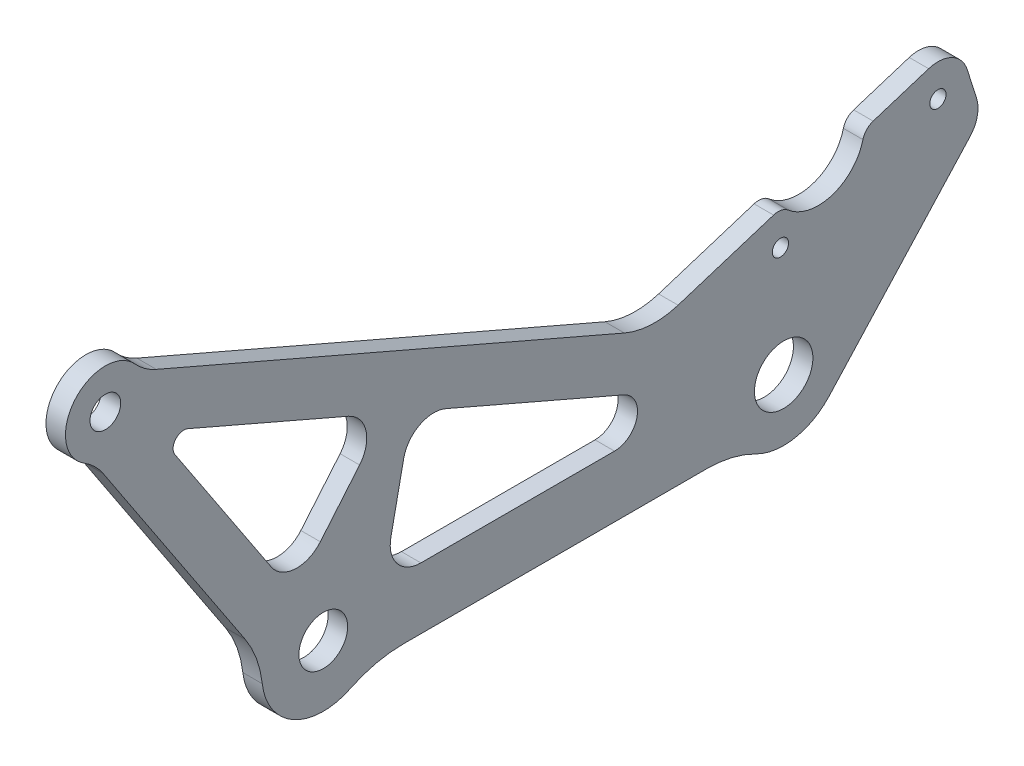
SolidWorks part; units mm, degrees
material "AISI 1020"
ref_plane "Front Plane" through (0, 0, 0) normal (0, 0, 1) x (1, 0, 0)
ref_plane "Top Plane" through (0, 0, 0) normal (0, 1, 0) x (1, 0, 0)
ref_plane "Right Plane" through (0, 0, 0) normal (1, 0, 0) x (0, 0, -1)
sketch "Sketch1" plane through (0, 0, 0) normal (1, 0, 0) x (0, 0, -1)
  line L0 (-60.7171, 0) -> (60.7171, 0)
  line L3 (0, -143.7223) -> (0, 143.7223) construction
  line L4 (-149.7529, 101.5535) -> (-94.5581, 18.1812)
  line L5 (-134.4049, 119.8783) -> (67.4524, 32.5212)
  line L6 (-75, 14) -> (75, 14) construction
  line L8 (-146, 114) -> (-75, 14) construction
  arc A20 (-134.4049, 119.8783) -> (-149.7529, 101.5535) centre (-146, 114) ccw
  arc A22 (-94.5581, 18.1812) -> (-60.7171, 0) centre (-75, 14) ccw
  arc A23 (60.7171, 0) -> (67.4524, 32.5212) centre (75, 14) ccw
  point P5 (0, 0)
  point P14 (0, 0)
  dimension "D3" = 20
  dimension "D5" = 13
  dimension "D6" = 20
  dimension "D4" = 127
  dimension "D7" = 254
  dimension "D10" = 6
  dimension "D11" = 6
  dimension "D9" = 3
  dimension "D12" = 3
  dimension "D13" = 6
  dimension "D14" = 6
  dimension "D2" = 150
  dimension "D8" = 122.6418
extrude "Boss-Extrude1" add sketch "Sketch1" along normal blind 6.35
hole_wizard "3/4 (0.75) Diameter Hole1" positions "Sketch4" profile "Sketch3" hole size "3/4" standard "ANSI Inch" end condition up to next
sketch "Sketch4" plane through (6.35, 0, 0) normal (1, 0, 0) x (0, 0, -1)
  point P5 (75, 14)
sketch "Sketch3" plane through (6.35, 14, -75) normal (0, 1, 0) x (0, 0, -1)
  line L0 (0, 0) -> (0, 6.35)
  line L1 (0, 6.35) -> (9.525, 6.35)
  line L2 (9.525, 6.35) -> (9.525, 0)
  line L5 (9.525, 0) -> (0, 0)
  line L11 (0, -6.35) -> (0, 107.95) construction
  dimension "Thru Hole Dia." = 19.05
  dimension "Thru Hole Depth" = 6.35
hole_wizard "Ø10.0 (10) Diameter Hole1" positions "Sketch9" profile "Sketch6" hole size "Ø10.0" standard "ANSI Metric" end condition up to next
sketch "Sketch9" plane through (6.35, 0, 0) normal (1, 0, 0) x (0, 0, -1)
  point P0 (-146, 114)
sketch "Sketch6" plane through (6.35, 114, 146) normal (0, 1, 0) x (0, 0, -1)
  line L0 (0, 0) -> (0, 6.35)
  line L1 (0, 6.35) -> (5, 6.35)
  line L2 (5, 6.35) -> (5, 0)
  line L5 (5, 0) -> (0, 0)
  line L11 (0, -6.35) -> (0, 107.95) construction
  dimension "Thru Hole Dia." = 10
  dimension "Thru Hole Depth" = 6.35
hole_wizard "Ø5/8\" Diameter Hole2" positions "Sketch16" profile "Sketch11" hole size "5/8" standard "ANSI Inch" end condition up to next
sketch "Sketch16" plane through (6.35, 0, 0) normal (1, 0, 0) x (0, 0, -1)
  line L0 (75, 14) -> (157.5513, 156.983)
  line L2 (0, 0) -> (0, 108.153) construction
  line L4 (-146, 114) -> (-119.4521, 194.8786)
  line L6 (-174.545, 70.324) -> (-178.0536, 59.6351) construction
  line L7 (-174.545, 70.324) -> (-178.0536, 59.6351) construction
  arc A0 (-94.5581, 18.1812) -> (-60.7171, 0) centre (-75, 14) ccw construction
  point P0 (-75, 14)
  dimension "D1" = 30
sketch "Sketch11" plane through (6.35, 14, 75) normal (0, 1, 0) x (0, 0, -1)
  line L0 (0, 0) -> (0, 6.35)
  line L1 (0, 6.35) -> (7.9375, 6.35)
  line L2 (7.9375, 6.35) -> (7.9375, 0)
  line L5 (7.9375, 0) -> (0, 0)
  line L11 (0, -6.35) -> (0, 107.95) construction
  dimension "Thru Hole Dia." = 15.875
  dimension "Thru Hole Depth" = 6.35
sketch "Sketch8" plane through (6.35, 0, 0) normal (1, 0, 0) x (0, 0, -1)
  line L2 (-54.5605, 67.8903) -> (-46.3008, 64.3157) construction
  line L3 (-52.9877, 32.028) -> (-48.7918, 52.2877)
  line L7 (-75.9573, 42.3434) -> (-63.1664, 57.6152)
  line L9 (-123.3455, 90.6494) -> (-91.9619, 43.2441)
  line L10 (-119.037, 95.7935) -> (-66.861, 73.2135)
  line L11 (19.8861, 20) -> (-43.1955, 20)
  line L12 (67.4524, 32.5212) -> (-134.4049, 119.8783) construction
  line L13 (-149.7529, 101.5535) -> (-94.5581, 18.1812) construction
  line L14 (-60.7171, 0) -> (60.7171, 0) construction
  line L15 (-84.5632, 32.0683) -> (-84.2827, 31.6447) construction
  line L16 (-55.4787, 20) -> (-55.9867, 20) construction
  line L17 (-54.5605, 67.8903) -> (-46.3008, 64.3157) construction
  line L18 (-35.0279, 59.4372) -> (22.8649, 34.3831)
  line L19 (-120.4271, 92.5814) -> (-104.3957, 79.1543) construction
  line L20 (19.8861, 27.5) -> (27.9693, 25.826) construction
  line L21 (-29.8567, 10) -> (10.3311, 10) construction
  arc A0 (-52.9877, 32.028) -> (-43.1955, 20) centre (-43.1955, 30) ccw
  arc A2 (-48.7918, 52.2877) -> (-35.0279, 59.4372) centre (-38.9996, 50.2597) cw
  arc A4 (-63.1664, 57.6152) -> (-66.861, 73.2135) centre (-70.8327, 64.0361) ccw
  arc A14 (-119.037, 95.7935) -> (-123.3455, 90.6494) centre (-120.4271, 92.5814) ccw
  arc A20 (-75.9573, 42.3434) -> (-91.9619, 43.2441) centre (-83.6236, 48.7643) cw
  arc A25 (-134.4049, 119.8783) -> (-149.7529, 101.5535) centre (-146, 114) ccw construction
  circle A27 centre (-146, 114) radius 5 construction
  arc A36 (-94.5581, 18.1812) -> (-60.7171, 0) centre (-75, 14) ccw construction
  circle A39 centre (-75, 14) radius 7.9375 construction
  arc A40 (19.8861, 20) -> (22.8649, 34.3831) centre (19.8861, 27.5) ccw
  circle A54 centre (-75, 14) radius 19.9375
  arc A55 (-55.9867, 20) -> (-84.2827, 31.6447) centre (-75, 14) ccw construction
  point P7 (-33.5049, 66.1162)
  point P19 (-33.4763, 76.1997)
  dimension "D8" = 8
  dimension "D9" = 12.0625
  dimension "D11" = 9
  dimension "D7" = 4
  dimension "D1" = 7
  dimension "D10" = 24.8576
  dimension "D2" = 15
  dimension "D12" = 10
  dimension "D13" = 14.6862
  dimension "D3" = 12
  dimension "D5" = 16
  dimension "D6" = 20
  dimension "D4" = 16
extrude "Cut-Extrude1" cut sketch "Sketch8" against normal up to next
fillet "Fillet1" radius 35 1 edges at (3.175, 18.1812, 94.5581)
fillet "Fillet3" radius 35 2 edges at (3.175, 32.5212, -67.4524) (3.175, 0, -60.7171)
fillet "Fillet4" radius 20 2 edges at (3.175, 101.5535, 149.7529) (3.175, 119.8783, 134.4049)
fillet "Fillet6" radius 40 1 edges at (3.175, 0, 60.7171)
sketch "Sketch17" plane through (0, 0, 0) normal (-1, 0, 0) x (0, 0, 1)
  line L0 (-31.692, 47.9971) -> (-74.6306, 61.6169)
  line L1 (-57.6351, 36.7697) -> (129.4114, 117.7173) construction
  line L2 (-134.8033, 70.2122) -> (-137.856, 60.5882)
  line L3 (-135.7084, 50.8215) -> (-89.7688, 0.5136)
  line L4 (-57.6351, 36.7697) -> (-31.692, 47.9971)
  line L6 (-84.0792, 16.8799) -> (-65.9208, 11.1201) construction
  line L7 (-100.5678, 75.614) -> (-71.9719, 66.5436) construction
  line L8 (-77.8799, 4.9208) -> (-72.1201, 23.0792) construction
  line L9 (-74.6306, 61.6169) -> (-101.2349, 70.0556) construction
  line L10 (-101.2349, 70.0556) -> (-122.2479, 76.7207)
  arc A0 (-73.7404, 33.9603) -> (-65.9164, -3.8182) centre (-75, 14) ccw construction
  arc A1 (-73.7404, 33.9603) -> (-57.6351, 36.7697) centre (-71.5361, 68.8908) ccw construction
  arc A2 (-73.7404, 33.9603) -> (-89.7688, 0.5136) centre (-75, 14) ccw
  arc A3 (-73.7404, 33.9603) -> (-57.6351, 36.7697) centre (-71.5361, 68.8908) ccw
  arc A4 (-137.856, 60.5882) -> (-135.7084, 50.8215) centre (-128.324, 57.5647) ccw
  arc A5 (-122.2479, 76.7207) -> (-134.8033, 70.2122) centre (-125.2713, 67.1887) ccw
  arc A6 (-101.2349, 70.0556) -> (-74.6306, 61.6169) centre (-86.2698, 71.0788) ccw
  circle A7 centre (-75, 14) radius 9.525 construction
  arc A8 (-71.9719, 66.5436) -> (-100.5678, 75.614) centre (-86.2698, 71.0788) ccw construction
  arc A9 (-100.5678, 75.614) -> (-101.2349, 70.0556) centre (-86.2698, 71.0788) ccw construction
  arc A10 (-74.6306, 61.6169) -> (-71.9719, 66.5436) centre (-86.2698, 71.0788) ccw construction
  point P15 (-75, 14)
  point P18 (-86.2698, 71.0788)
  point P26 (-139.6016, 55.0849)
  point P29 (-131.7798, 79.7442)
  point P31 (-75, 14)
  dimension "D5" = 10
  dimension "D1" = 41
  dimension "D2" = 45.5
  dimension "D3" = 120
  dimension "D4" = 74
  dimension "D6" = 30
  dimension "D7" = 51
  dimension "D8" = 28
extrude "Boss-Extrude2" add sketch "Sketch17" against normal up to surface (6.35 mm away) up to face at (6.35, 36.3112, 22.6592)
hole_wizard "M5 Clearance Hole1" positions "Sketch21" profile "Sketch19" hole size "M5" standard "ANSI Metric" end condition up to next
sketch "Sketch21" plane through (0, 0, 0) normal (-1, 0, 0) x (0, 0, 1)
  line L0 (-125.2509, 66.6577) -> (-73.9498, 50.3854) construction
  line L2 (-31.692, 47.9971) -> (-74.6306, 61.6169) construction
  line L3 (-75, 14) -> (-64.4178, 47.3619) construction
  line L5 (-134.8033, 70.2122) -> (-137.856, 60.5882) construction
  point P1 (-125.2509, 66.6577)
  point P3 (-73.9498, 50.3854)
  dimension "D1" = 35
  dimension "D2" = 10
  dimension "D3" = 53.82
sketch "Sketch19" plane through (0, 66.6577, -125.2509) normal (0, 1, 0) x (0, 0, 1)
  line L0 (0, 0) -> (0, 6.35)
  line L1 (0, 6.35) -> (2.65, 6.35)
  line L2 (2.65, 6.35) -> (2.65, 0)
  line L5 (2.65, 0) -> (0, 0)
  line L11 (0, -6.35) -> (0, 107.95) construction
  dimension "Thru Hole Dia." = 5.3
  dimension "Thru Hole Depth" = 6.35
fillet "Fillet7" radius 25 1 edges at (3.175, 47.9971, -31.692) type face fillet first side face at (3.175, 54.807, -53.1613) second side face at (3.175, 82.8572, 48.8597)
fillet "Fillet8" radius 5 2 edges at (3.175, 61.6169, -74.6306) (3.175, 70.0556, -101.2349)
equation "\"D11@Sketch1\"=\"D10@Sketch1\""
equation "\"D12@Sketch1\"=\"D9@Sketch1\""
equation "\"D14@Sketch1\"=\"D13@Sketch1\""
